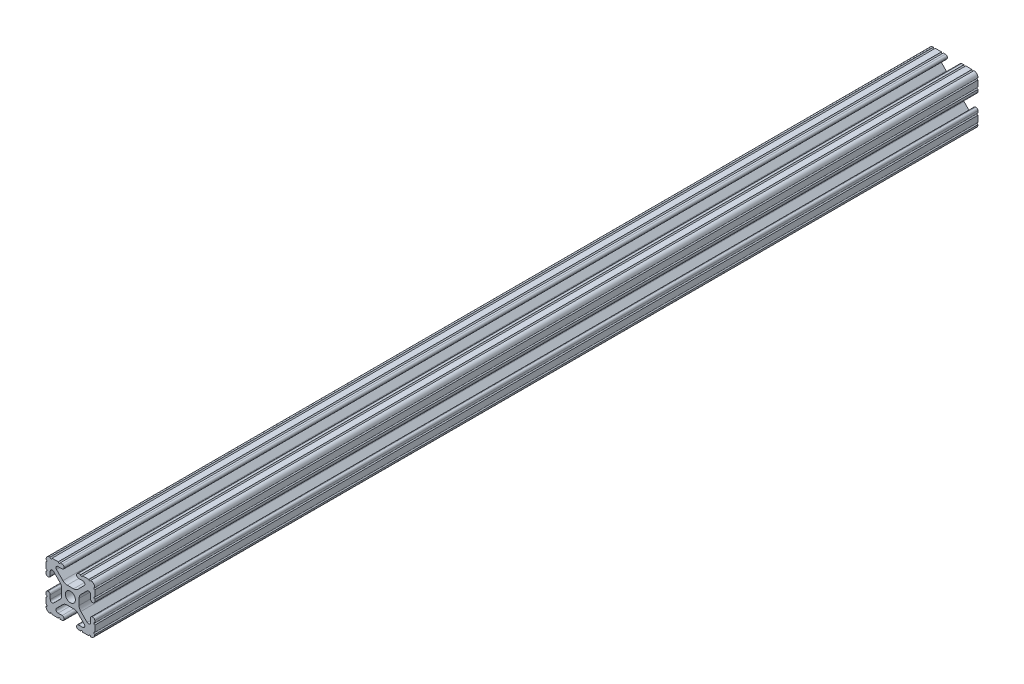
SolidWorks part; units mm, degrees
ref_plane "Front Plane" through (0, 0, 0) normal (0, 0, 1) x (1, 0, 0)
ref_plane "Top Plane" through (0, 0, 0) normal (0, 1, 0) x (1, 0, 0)
ref_plane "Right Plane" through (0, 0, 0) normal (1, 0, 0) x (0, 0, -1)
sketch "Sketch1" plane through (0, 0, 0) normal (0, 0, 1) x (1, 0, 0)
  line L88 (-7.1797, -8.6452) -> (-3.9523, -5.4237)
  line L89 (-1.7093, -4.4958) -> (1.7093, -4.4958)
  line L90 (3.9523, -5.4237) -> (7.1797, -8.6452)
  line L91 (6.4164, -10.4902) -> (4.2875, -10.4902)
  line L92 (3.2385, -11.5392) -> (3.2385, -11.651)
  line L93 (4.2875, -12.7) -> (5.3171, -12.7)
  line L94 (6.3331, -12.7) -> (9.5504, -12.7)
  line L95 (12.7, -9.5504) -> (12.7, -6.3331)
  line L96 (12.7, -5.3171) -> (12.7, -4.2875)
  line L97 (11.651, -3.2385) -> (11.5392, -3.2385)
  line L98 (10.4902, -4.2875) -> (10.4902, -6.4021)
  line L99 (8.7371, -7.1294) -> (5.441, -3.8408)
  line L100 (4.5085, -1.5932) -> (4.5085, 1.5932)
  line L101 (5.441, 3.8408) -> (8.7371, 7.1294)
  line L102 (10.4902, 6.4021) -> (10.4902, 4.2875)
  line L103 (11.5392, 3.2385) -> (11.651, 3.2385)
  line L104 (12.7, 4.2875) -> (12.7, 5.3171)
  line L105 (12.7, 6.3331) -> (12.7, 9.5504)
  line L106 (9.5504, 12.7) -> (6.3331, 12.7)
  line L107 (5.3171, 12.7) -> (4.2875, 12.7)
  line L108 (3.2385, 11.651) -> (3.2385, 11.5392)
  line L109 (4.2875, 10.4902) -> (6.4768, 10.4902)
  line L110 (7.207, 8.7244) -> (3.8983, 5.4232)
  line L111 (1.6558, 4.4958) -> (-1.6558, 4.4958)
  line L112 (-3.8983, 5.4232) -> (-7.207, 8.7244)
  line L113 (-6.4768, 10.4902) -> (-4.2875, 10.4902)
  line L114 (-3.2385, 11.5392) -> (-3.2385, 11.651)
  line L115 (-4.2875, 12.7) -> (-5.3171, 12.7)
  line L116 (-6.3331, 12.7) -> (-9.5504, 12.7)
  line L117 (-12.7, 9.5504) -> (-12.7, 6.3331)
  line L118 (-12.7, 5.3171) -> (-12.7, 4.2875)
  line L119 (-11.651, 3.2385) -> (-11.5392, 3.2385)
  line L120 (-10.4902, 4.2875) -> (-10.4902, 6.4021)
  line L121 (-8.7371, 7.1294) -> (-5.441, 3.8408)
  line L122 (-4.5085, 1.5932) -> (-4.5085, -1.5932)
  line L123 (-5.441, -3.8408) -> (-8.7371, -7.1294)
  line L124 (-10.4902, -6.4021) -> (-10.4902, -4.2875)
  line L125 (-11.5392, -3.2385) -> (-11.651, -3.2385)
  line L126 (-12.7, -4.2875) -> (-12.7, -5.3171)
  line L127 (-12.7, -6.3331) -> (-12.7, -9.5504)
  line L128 (-9.5504, -12.7) -> (-6.3331, -12.7)
  line L129 (-5.3171, -12.7) -> (-4.2875, -12.7)
  line L130 (-3.2385, -11.651) -> (-3.2385, -11.5392)
  line L131 (-4.2875, -10.4902) -> (-6.4164, -10.4902)
  circle A1 centre (0, 0) radius 2.6035
  arc A104 (-7.1797, -8.6452) -> (-6.4164, -10.4902) centre (-6.4164, -9.4098) ccw
  arc A105 (-1.7093, -4.4958) -> (-3.9523, -5.4237) centre (-1.7093, -7.6708) ccw
  arc A106 (3.9523, -5.4237) -> (1.7093, -4.4958) centre (1.7093, -7.6708) ccw
  arc A107 (6.4164, -10.4902) -> (7.1797, -8.6452) centre (6.4164, -9.4098) ccw
  arc A108 (4.2875, -10.4902) -> (3.2385, -11.5392) centre (4.2875, -11.5392) ccw
  arc A109 (3.2385, -11.651) -> (4.2875, -12.7) centre (4.2875, -11.651) ccw
  arc A110 (6.3331, -12.7) -> (5.3171, -12.7) centre (5.8251, -12.7) ccw
  arc A111 (10.5664, -12.6998) -> (9.5504, -12.7) centre (10.0584, -12.7) ccw
  arc A112 (10.5664, -12.6998) -> (12.6998, -10.5664) centre (10.5918, -10.5918) ccw
  arc A113 (12.7, -9.5504) -> (12.6998, -10.5664) centre (12.7, -10.0584) ccw
  arc A114 (12.7, -5.3171) -> (12.7, -6.3331) centre (12.7, -5.8251) ccw
  arc A115 (12.7, -4.2875) -> (11.651, -3.2385) centre (11.651, -4.2875) ccw
  arc A116 (11.5392, -3.2385) -> (10.4902, -4.2875) centre (11.5392, -4.2875) ccw
  arc A117 (8.7371, -7.1294) -> (10.4902, -6.4021) centre (9.4628, -6.4021) ccw
  arc A118 (4.5085, -1.5932) -> (5.441, -3.8408) centre (7.6835, -1.5932) ccw
  arc A119 (5.441, 3.8408) -> (4.5085, 1.5932) centre (7.6835, 1.5932) ccw
  arc A120 (10.4902, 6.4021) -> (8.7371, 7.1294) centre (9.4628, 6.4021) ccw
  arc A121 (10.4902, 4.2875) -> (11.5392, 3.2385) centre (11.5392, 4.2875) ccw
  arc A122 (11.651, 3.2385) -> (12.7, 4.2875) centre (11.651, 4.2875) ccw
  arc A123 (12.7, 6.3331) -> (12.7, 5.3171) centre (12.7, 5.8251) ccw
  arc A124 (12.6998, 10.5664) -> (12.7, 9.5504) centre (12.7, 10.0584) ccw
  arc A125 (12.6998, 10.5664) -> (10.5664, 12.6998) centre (10.5918, 10.5918) ccw
  arc A126 (9.5504, 12.7) -> (10.5664, 12.6998) centre (10.0584, 12.7) ccw
  arc A127 (5.3171, 12.7) -> (6.3331, 12.7) centre (5.8251, 12.7) ccw
  arc A128 (4.2875, 12.7) -> (3.2385, 11.651) centre (4.2875, 11.651) ccw
  arc A129 (3.2385, 11.5392) -> (4.2875, 10.4902) centre (4.2875, 11.5392) ccw
  arc A130 (7.207, 8.7244) -> (6.4768, 10.4902) centre (6.4768, 9.4563) ccw
  arc A131 (1.6558, 4.4958) -> (3.8983, 5.4232) centre (1.6558, 7.6708) ccw
  arc A132 (-3.8983, 5.4232) -> (-1.6558, 4.4958) centre (-1.6558, 7.6708) ccw
  arc A133 (-6.4768, 10.4902) -> (-7.207, 8.7244) centre (-6.4768, 9.4563) ccw
  arc A134 (-4.2875, 10.4902) -> (-3.2385, 11.5392) centre (-4.2875, 11.5392) ccw
  arc A135 (-3.2385, 11.651) -> (-4.2875, 12.7) centre (-4.2875, 11.651) ccw
  arc A136 (-6.3331, 12.7) -> (-5.3171, 12.7) centre (-5.8251, 12.7) ccw
  arc A137 (-10.5664, 12.6998) -> (-9.5504, 12.7) centre (-10.0584, 12.7) ccw
  arc A138 (-10.5664, 12.6998) -> (-12.6998, 10.5664) centre (-10.5918, 10.5918) ccw
  arc A139 (-12.7, 9.5504) -> (-12.6998, 10.5664) centre (-12.7, 10.0584) ccw
  arc A140 (-12.7, 5.3171) -> (-12.7, 6.3331) centre (-12.7, 5.8251) ccw
  arc A141 (-12.7, 4.2875) -> (-11.651, 3.2385) centre (-11.651, 4.2875) ccw
  arc A142 (-11.5392, 3.2385) -> (-10.4902, 4.2875) centre (-11.5392, 4.2875) ccw
  arc A143 (-8.7371, 7.1294) -> (-10.4902, 6.4021) centre (-9.4628, 6.4021) ccw
  arc A144 (-4.5085, 1.5932) -> (-5.441, 3.8408) centre (-7.6835, 1.5932) ccw
  arc A145 (-5.441, -3.8408) -> (-4.5085, -1.5932) centre (-7.6835, -1.5932) ccw
  arc A146 (-10.4902, -6.4021) -> (-8.7371, -7.1294) centre (-9.4628, -6.4021) ccw
  arc A147 (-10.4902, -4.2875) -> (-11.5392, -3.2385) centre (-11.5392, -4.2875) ccw
  arc A148 (-11.651, -3.2385) -> (-12.7, -4.2875) centre (-11.651, -4.2875) ccw
  arc A149 (-12.7, -6.3331) -> (-12.7, -5.3171) centre (-12.7, -5.8251) ccw
  arc A150 (-12.6998, -10.5664) -> (-12.7, -9.5504) centre (-12.7, -10.0584) ccw
  arc A151 (-12.6998, -10.5664) -> (-10.5664, -12.6998) centre (-10.5918, -10.5918) ccw
  arc A152 (-9.5504, -12.7) -> (-10.5664, -12.6998) centre (-10.0584, -12.7) ccw
  arc A153 (-5.3171, -12.7) -> (-6.3331, -12.7) centre (-5.8251, -12.7) ccw
  arc A154 (-4.2875, -12.7) -> (-3.2385, -11.651) centre (-4.2875, -11.651) ccw
  arc A155 (-3.2385, -11.5392) -> (-4.2875, -10.4902) centre (-4.2875, -11.5392) ccw
extrude "Boss-Extrude1" add sketch "Sketch1" along normal mid plane 459.74
ref_plane "Plane1" through (0, 0, 0) normal (0, 1, 0) x (1, 0, 0)
